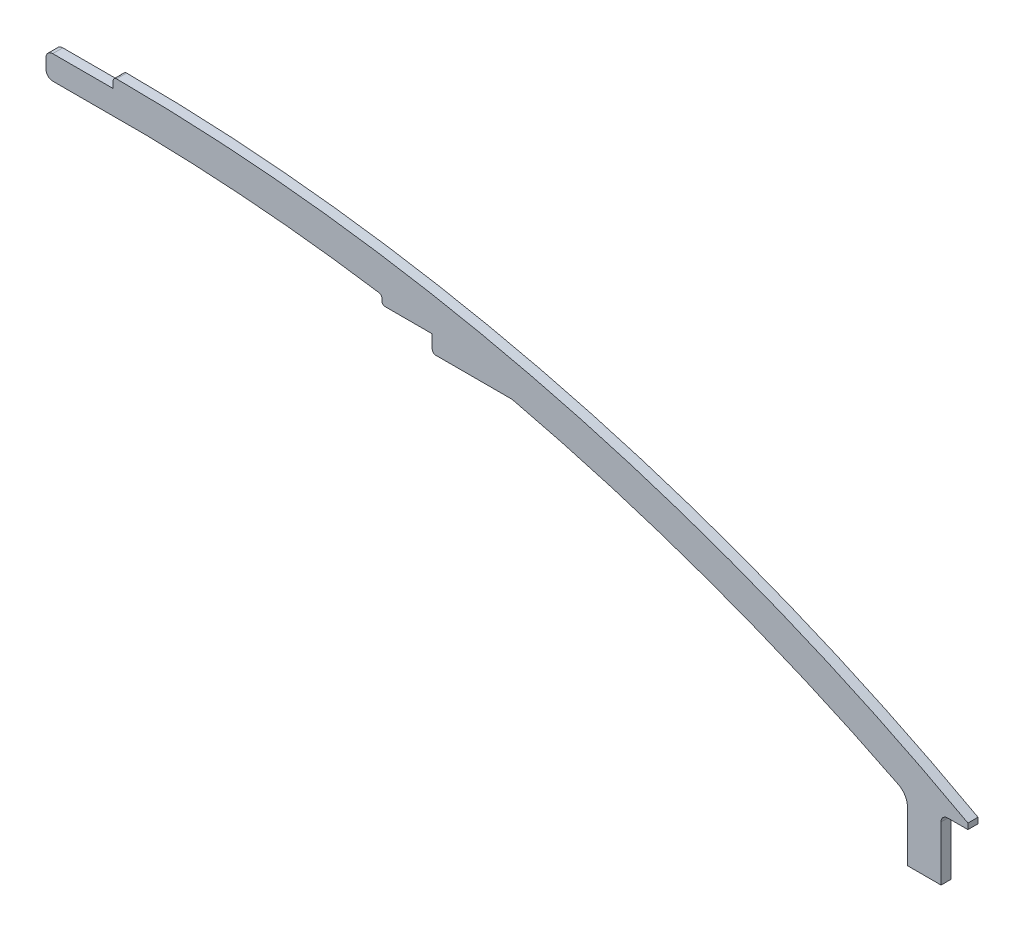
SolidWorks part; units mm, degrees
ref_plane "Front Plane" through (0, 0, 0) normal (0, 0, 1) x (1, 0, 0)
ref_plane "Top Plane" through (0, 0, 0) normal (0, 1, 0) x (1, 0, 0)
ref_plane "Right Plane" through (0, 0, 0) normal (1, 0, 0) x (0, 0, -1)
sketch "Sketch1" plane through (0, 0, 0) normal (0, 0, 1) x (1, 0, 0)
  line L0 (-45, 0) -> (45, 0) construction
  line L1 (300, -65.3534) -> (300, -85.3534)
  line L2 (-45, -150.7069) -> (45, -150.7069) construction
  line L3 (-45, 0) -> (-45, -150.7069) construction
  line L4 (45, 0) -> (45, -150.7069) construction
  line L5 (0, 0) -> (0, -150.7069)
  line L6 (45, 0) -> (0, 0)
  line L7 (0, -150.7069) -> (45, -150.7069)
  arc A0 (45, 0) -> (300, -65.3534) centre (45, -530.1639) cw
  arc A1 (-28.1177, 0) -> (35.3823, 0) centre (3.6323, -0.0236) cw construction
  arc A2 (45, -150.7069) -> (300, -85.3534) centre (45, 379.457) ccw
  point P4 (0, 0)
  dimension "D2" = 300
  dimension "D3" = 31.75
  dimension "D5" = 150.7069
  dimension "D1" = 90
  dimension "D4" = 20
sketch "Sketch2" plane through (0, 0, 0) normal (0, 0, 1) x (1, 0, 0)
  line L0 (299.5, -67.3534) -> (293.5, -67.3534)
  line L1 (291.5, -69.3534) -> (291.5, -85.6495)
  line L2 (54.9033, -10.5962) -> (27, -10.5962)
  line L3 (25, -8.5962) -> (25, -5.5)
  line L4 (300, -65.3534) -> (300, -85.3534) construction
  line L5 (300, -65.3534) -> (300, -85.3534) construction
  line L6 (299.5, -65.6495) -> (299.5, -67.3534)
  line L7 (291.5, -85.6495) -> (281.5, -85.6495)
  line L8 (45, -1.5009) -> (45, -3.5)
  line L9 (45, 0) -> (45, -150.7069) construction
  line L10 (45, -3.5) -> (27, -3.5)
  line L11 (281.5, -85.6495) -> (281.5, -70.5046)
  line L12 (45, -0.5) -> (0.5, -0.5)
  line L13 (0.5, -0.5) -> (0.5, -150.2069)
  line L14 (0.5, -150.2069) -> (45, -150.2069)
  line L15 (299.5, -85.0574) -> (299.5, -65.6495)
  line L20 (55, -13.5) -> (25, -13.5) construction
  line L21 (55, -10.5962) -> (55, -13.5) construction
  line L22 (140, -19.2573) -> (140, -23.2573)
  line L23 (140, -19.2573) -> (126, -19.2573)
  line L24 (125, -18.2573) -> (125, -17.5517)
  line L25 (141, -24.2573) -> (163.7816, -24.2573)
  line L26 (0, 0) -> (0, -150.7069) construction
  line L27 (45, -3.5) -> (25, -3.5) construction
  line L28 (45, -0.5) -> (45, -3.5) construction
  arc A0 (278.749, -66.039) -> (163.7816, -24.2573) centre (45, -530.1639) ccw
  arc A1 (294.6951, -74.4195) -> (55, -10.5962) centre (45, -530.1639) ccw construction
  arc A2 (55.0976, -10.5981) -> (54.9033, -10.5962) centre (54.9033, -20.5962) ccw
  arc A3 (281.5, -70.5046) -> (278.749, -66.039) centre (276.5, -70.5046) ccw
  arc A4 (293.5, -67.3534) -> (291.5, -69.3534) centre (293.5, -69.3534) ccw
  arc A5 (124.1523, -16.5634) -> (55.0976, -10.5981) centre (45, -530.1639) ccw
  arc A6 (45, -150.2069) -> (299.5, -85.0574) centre (45, 379.457) ccw
  arc A7 (299.5, -65.6495) -> (45, -0.5) centre (45, -530.1639) ccw
  arc A9 (299.5, -65.6495) -> (46.0019, -0.5009) centre (45, -530.1639) ccw
  arc A10 (125, -16.6947) -> (163.7816, -24.2573) centre (45, -530.1639) cw construction
  arc A11 (140, -23.2573) -> (141, -24.2573) centre (141, -23.2573) ccw
  arc A12 (126, -19.2573) -> (125, -18.2573) centre (126, -18.2573) cw
  arc A13 (125, -17.5517) -> (124.1523, -16.5634) centre (124, -17.5517) ccw
  arc A14 (27, -10.5962) -> (25, -8.5962) centre (27, -8.5962) cw
  arc A15 (27, -3.5) -> (25, -5.5) centre (27, -5.5) ccw
  arc A16 (299.5, -65.6495) -> (45, -0.5) centre (45, -530.1639) ccw construction
  arc A17 (45, -1.5009) -> (46.0019, -0.5009) centre (46, -1.5009) cw
  point P26 (300, -75.3534)
  point P33 (291.5, -67.3534)
  point P40 (0, 0)
  point P43 (140, -24.2573)
  point P48 (125, -19.2573)
  point P57 (25, -3.5)
  dimension "D5" = 10
  dimension "D10" = 5
  dimension "D11" = 2
  dimension "D16" = 1
  dimension "D17" = 2
  dimension "D18" = 1
  dimension "D2" = 20
  dimension "D3" = 3
  dimension "D6" = 7.0962
  dimension "D7" = 8
  dimension "D8" = 8
  dimension "D9" = 10
  dimension "D12" = 20
  dimension "D13" = 15
  dimension "D14" = 5
  dimension "D15" = 140
  dimension "D1" = 0.5
  dimension "D4" = 10
extrude "Boss-Extrude1" add sketch "Sketch2" along normal mid plane 3
